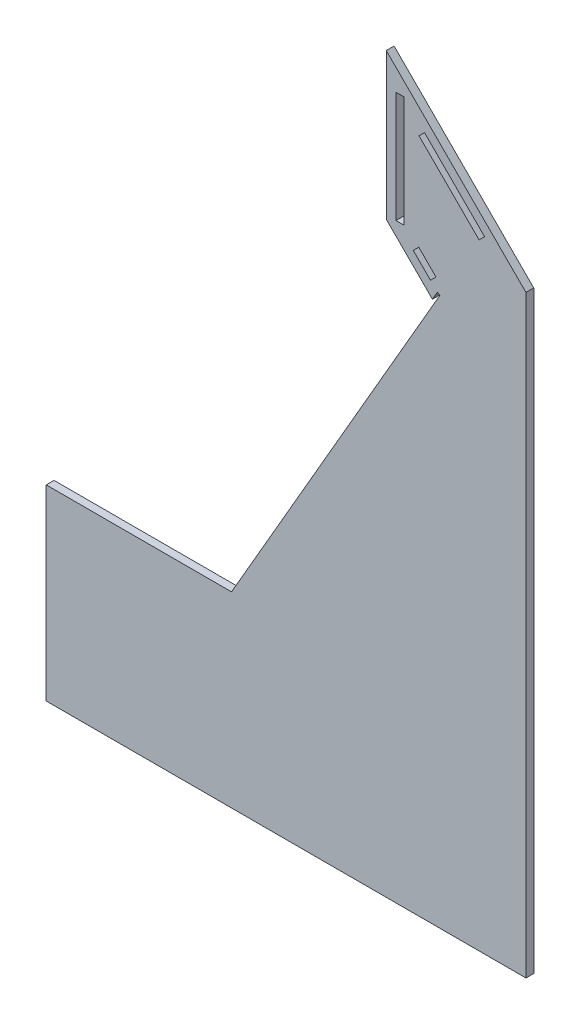
SolidWorks part; units mm, degrees
ref_plane "Front Plane" through (0, 0, 0) normal (0, 0, 1) x (1, 0, 0)
ref_plane "Top Plane" through (0, 0, 0) normal (0, 1, 0) x (1, 0, 0)
ref_plane "Right Plane" through (0, 0, 0) normal (1, 0, 0) x (0, 0, -1)
sketch "Sketch1" plane through (0, 0, 0) normal (0, 0, 1) x (1, 0, 0)
  line L0 (0, 192) -> (190, 192) construction
  line L1 (0, 0) -> (492, 0)
  line L2 (0, 0) -> (0, 192)
  line L3 (0, 192) -> (190, 192)
  line L5 (190, 192) -> (398.25, 552.6996)
  line L6 (398.25, 552.6996) -> (348.7525, 602.1971)
  line L7 (348.7525, 602.1971) -> (348.7525, 752.1971)
  line L8 (348.7525, 752.1971) -> (492, 608.9496)
  line L9 (492, 608.9496) -> (492, 0)
  line L13 (398.25, 552.6996) -> (403.7528, 562.2307)
  line L14 (403.7528, 562.2307) -> (401.1547, 563.7307)
  line L15 (401.1547, 563.7307) -> (396.0538, 554.8957)
  line L16 (191.1547, 200) -> (401.1547, 563.7307) construction
  line L17 (376.406, 588.4794) -> (394.0836, 570.8017) construction
  line L18 (394.0836, 570.8017) -> (399.7405, 576.4586) construction
  line L19 (399.7405, 576.4586) -> (382.0628, 594.1363) construction
  line L20 (382.0628, 594.1363) -> (376.406, 588.4794) construction
  line L29 (366.7283, 606.1571) -> (366.7283, 720.0871) construction
  line L30 (366.7283, 720.0871) -> (358.7283, 720.0871) construction
  line L31 (358.7283, 720.0871) -> (358.7283, 606.1571) construction
  line L32 (358.7283, 606.1571) -> (366.7283, 606.1571) construction
  line L33 (382.2846, 693.217) -> (443.9161, 631.5856) construction
  line L34 (443.9161, 631.5856) -> (449.5729, 637.2424) construction
  line L35 (449.5729, 637.2424) -> (387.9415, 698.8739) construction
  line L36 (387.9415, 698.8739) -> (382.2846, 693.217) construction
  line L37 (376.406, 588.4794) -> (394.0836, 570.8017)
  line L38 (394.0836, 570.8017) -> (399.7405, 576.4586)
  line L39 (399.7405, 576.4586) -> (382.0628, 594.1363)
  line L40 (382.0628, 594.1363) -> (376.406, 588.4794)
  line L41 (366.7283, 606.1571) -> (366.7283, 720.0871)
  line L42 (366.7283, 720.0871) -> (358.7283, 720.0871)
  line L43 (358.7283, 720.0871) -> (358.7283, 606.1571)
  line L44 (358.7283, 606.1571) -> (366.7283, 606.1571)
  line L45 (382.2846, 693.217) -> (443.9161, 631.5856)
  line L46 (443.9161, 631.5856) -> (449.5729, 637.2424)
  line L47 (449.5729, 637.2424) -> (387.9415, 698.8739)
  line L48 (387.9415, 698.8739) -> (382.2846, 693.217)
  dimension "D3" = 60
  dimension "D1" = 492
  dimension "D2" = 192
  dimension "D4" = 416.5
  dimension "D5" = 190
  dimension "D6" = 150
  dimension "D7" = 70
  dimension "D8" = 105
extrude "Boss-Extrude1" add sketch "Sketch1" along normal blind 8 contours L5 | L15 L14 L13 L5 L3 L2 L1 L9 L8 L7 L6 region at (314.4165, 236.9247, 0)
